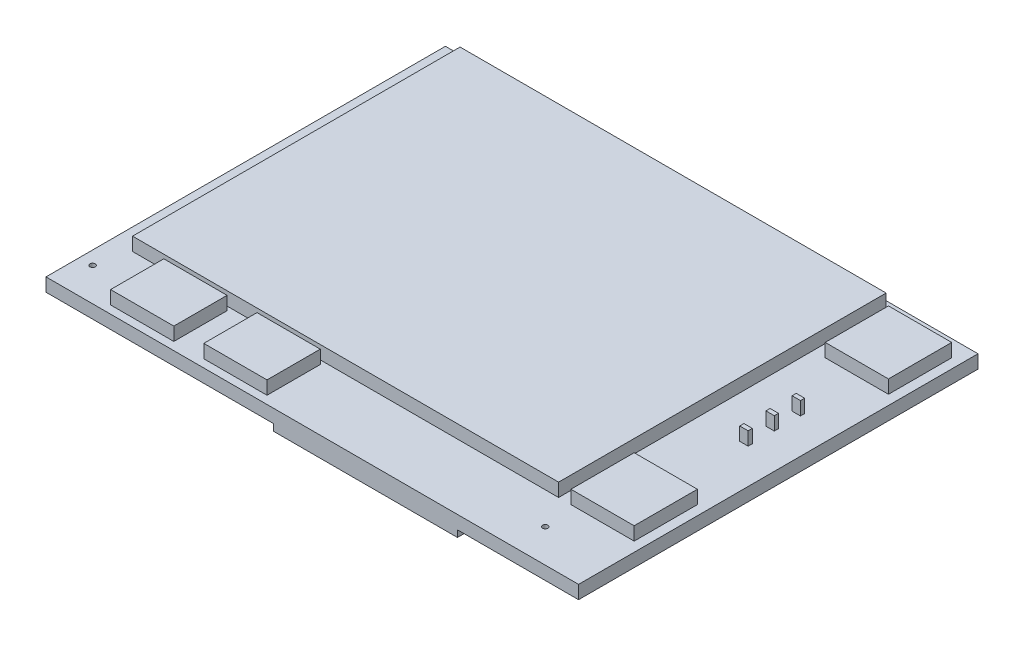
SolidWorks part; units mm, degrees
ref_plane "Front Plane" through (0, 0, 0) normal (0, 0, 1) x (1, 0, 0)
ref_plane "Top Plane" through (0, 0, 0) normal (0, 1, 0) x (1, 0, 0)
ref_plane "Right Plane" through (0, 0, 0) normal (1, 0, 0) x (0, 0, -1)
sketch "Sketch1" plane through (0, 0, 0) normal (0, 1, 0) x (1, 0, 0)
  line L1 (-50.8, -38.1) -> (50.8, -38.1)
  line L2 (-50.8, -38.1) -> (-50.8, 38.1)
  line L3 (-50.8, 38.1) -> (50.8, 38.1)
  line L4 (50.8, -38.1) -> (50.8, 38.1)
  line L5 (-50.8, -38.1) -> (50.8, 38.1) construction
  line L6 (-50.8, 38.1) -> (50.8, -38.1) construction
  point P0 (0, 0)
  dimension "D1" = 101.6
  dimension "D2" = 76.2
extrude "Boss-Extrude1" add sketch "Sketch1" along normal blind 2.54
sketch "Sketch2" plane through (0, 2.54, 0) normal (0, 1, 0) x (1, 0, 0)
  line L0 (42.545, 6.693) -> (44.145, 6.693)
  line L1 (-46.736, 36.83) -> (34.544, 36.83)
  line L2 (-46.736, 36.83) -> (-46.736, -25.654)
  line L3 (-46.736, -25.654) -> (34.544, -25.654)
  line L4 (34.544, 36.83) -> (34.544, -25.654)
  line L5 (36.8935, 34.925) -> (48.9585, 34.925)
  line L6 (36.8935, 34.925) -> (36.8935, 22.86)
  line L7 (36.8935, 22.86) -> (48.9585, 22.86)
  line L8 (48.9585, 34.925) -> (48.9585, 22.86)
  line L9 (36.8935, -13.589) -> (48.9585, -13.589)
  line L10 (36.8935, -13.589) -> (36.8935, -25.654)
  line L11 (36.8935, -25.654) -> (48.9585, -25.654)
  line L12 (48.9585, -13.589) -> (48.9585, -25.654)
  line L13 (42.545, 1.702) -> (44.145, 1.702)
  line L14 (42.545, 1.702) -> (42.545, 0.902)
  line L15 (42.545, 0.902) -> (44.145, 0.902)
  line L16 (44.145, 1.702) -> (44.145, 0.902)
  line L17 (42.545, 6.693) -> (42.545, 5.893)
  line L18 (42.545, 5.893) -> (44.145, 5.893)
  line L19 (44.145, 6.693) -> (44.145, 5.893)
  line L20 (42.545, 11.684) -> (44.145, 11.684)
  line L21 (42.545, 11.684) -> (42.545, 10.884)
  line L22 (42.545, 10.884) -> (44.145, 10.884)
  line L23 (44.145, 11.684) -> (44.145, 10.884)
  line L24 (-40.005, -26.416) -> (-27.94, -26.416)
  line L25 (-22.225, -26.416) -> (-10.16, -26.416)
  line L26 (-22.225, -26.416) -> (-22.225, -36.576)
  line L27 (-22.225, -36.576) -> (-10.16, -36.576)
  line L28 (-10.16, -26.416) -> (-10.16, -36.576)
  line L29 (-40.005, -26.416) -> (-40.005, -36.576)
  line L30 (-40.005, -36.576) -> (-27.94, -36.576)
  line L31 (-27.94, -26.416) -> (-27.94, -36.576)
  line L32 (-50.8, 38.1) -> (-50.8, -38.1) construction
  line L33 (50.8, 38.1) -> (-50.8, 38.1) construction
  line L34 (-50.8, -38.1) -> (50.8, -38.1) construction
  line L35 (50.8, -38.1) -> (50.8, 38.1) construction
  circle A0 centre (-48.26, -31.75) radius 0.508
  circle A1 centre (38.1, 36.83) radius 0.508
  circle A2 centre (38.1, -31.75) radius 0.508
  point P42 (-43.7927, -2.3753)
  point P45 (41.336, -31.75)
  point P48 (12.1677, 40.8608)
  point P49 (0, 0)
  dimension "D32" = 1.016
  dimension "D1" = 81.28
  dimension "D2" = 62.484
  dimension "D4" = 0
  dimension "D5" = 12.065
  dimension "D6" = 1.6
  dimension "D7" = 0.8
  dimension "D8" = 12.065
  dimension "D9" = 10.16
  dimension "D10" = 1.27
  dimension "D11" = 1.524
  dimension "D12" = 1.524
  dimension "D13" = 5.715
  dimension "D14" = 4.064
  dimension "D15" = 10.795
  dimension "D16" = 12.065
  dimension "D17" = 10.16
  dimension "D18" = 0
  dimension "D19" = 0
  dimension "D20" = 4.191
  dimension "D21" = 4.191
  dimension "D23" = 0
  dimension "D24" = 1.6
  dimension "D25" = 0.8
  dimension "D26" = 0.8
  dimension "D27" = 1.6
  dimension "D28" = 11.176
  dimension "D29" = 0
  dimension "D30" = 1.8415
  dimension "D31" = 5.6515
  dimension "D33" = 6.35
  dimension "D34" = 2.54
  dimension "D35" = 1.27
  dimension "D36" = 88.9
  dimension "D37" = 12.7
  dimension "D38" = 6.35
  dimension "D39" = 12.065
  dimension "D40" = 3.175
sketch "Sketch3" plane through (0, 0, 0) normal (0, -1, 0) x (1, 0, 0)
  line L1 (-7.366, 38.1) -> (27.686, 38.1)
  line L2 (-7.366, 38.1) -> (-7.366, -18.034)
  line L3 (-7.366, -18.034) -> (27.686, -18.034)
  line L4 (27.686, 38.1) -> (27.686, -18.034)
  line L5 (-50.8, 38.1) -> (50.8, 38.1) construction
  line L6 (-50.8, -38.1) -> (-50.8, 38.1) construction
  line L7 (-27.178, -38.1) -> (-27.178, -27.1)
  line L8 (-27.178, -38.1) -> (-17.778, -38.1)
  line L9 (-17.778, -38.1) -> (-17.778, -27.1)
  line L10 (-27.178, -27.1) -> (-17.778, -27.1)
  line L12 (50.8, -38.1) -> (-50.8, -38.1) construction
  dimension "D1" = 35.052
  dimension "D2" = 56.134
  dimension "D3" = 0
  dimension "D4" = 11
  dimension "D5" = 9.4
  dimension "D6" = 0
  dimension "D7" = 23.622
  dimension "D8" = 43.434
extrude "Boss-Extrude4" add sketch "Sketch3" along normal blind 1.27
extrude "Boss-Extrude5" add sketch "Sketch2" along normal blind 2.54 contours L31 L24 L29 L30 | L28 L25 L26 L27 | L4 L1 L2 L3 | L12 L9 L10 L11 | L8 L5 L6 L7 | L16 L13 L14 L15 | L19 L0 L17 L18 | L23 L20 L21 L22 region at (43.345, 2.54, -6.293) region at (-6.096, 2.54, -5.588) region at (42.926, 2.54, -28.8925) region at (42.926, 2.54, 19.6215) region at (43.345, 2.54, -1.302) region at (43.345, 2.54, -11.284) region at (-33.9725, 2.54, 31.496) region at (-16.1925, 2.54, 31.496)
extrude "Cut-Extrude1" cut sketch "Sketch2<3>" against normal through all contours A0 | A2 | A1 region at (-48.26, 2.54, 31.75) region at (38.1, 2.54, -36.83) region at (38.1, 2.54, 31.75)
sketch "Sketch2<3>" plane through (0, 2.54, 0) normal (0, 1, 0) x (1, 0, 0) same geometry as "Sketch2"
